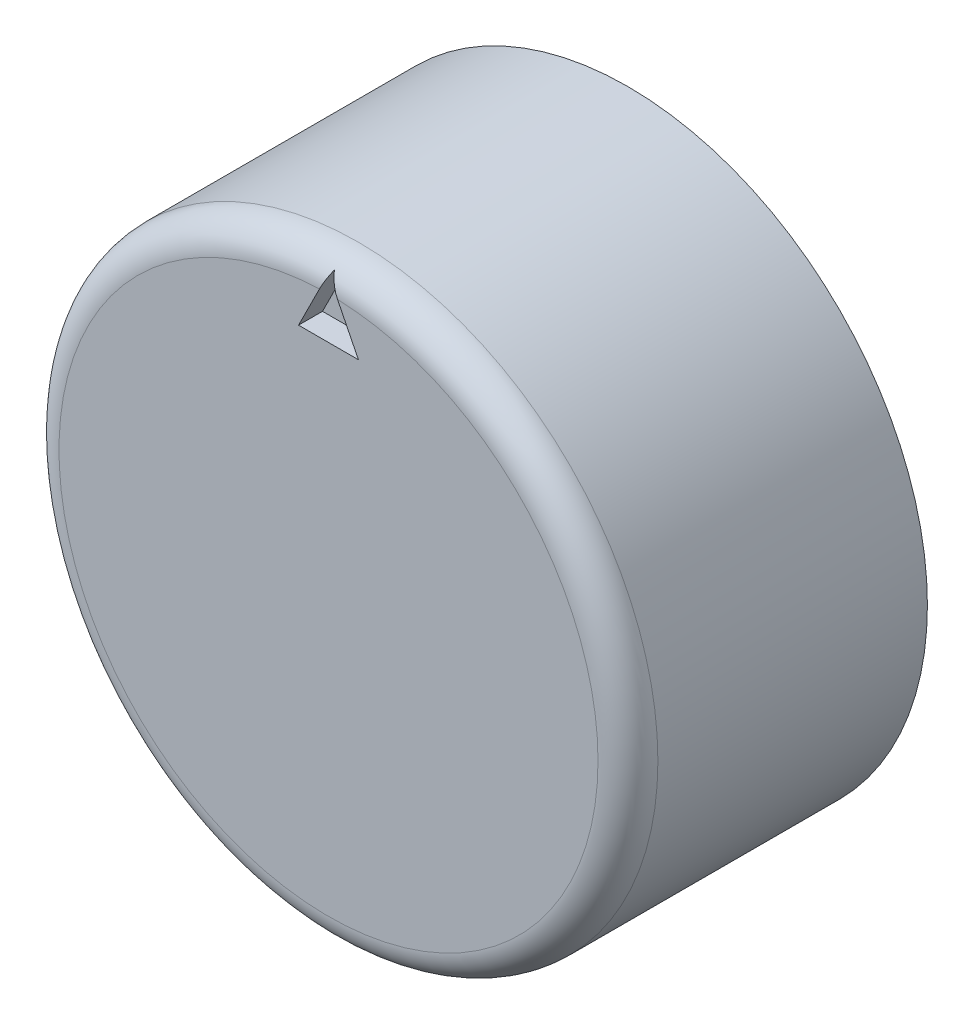
SolidWorks part; units mm, degrees
ref_plane "Front Plane" through (0, 0, 0) normal (0, 0, 1) x (1, 0, 0)
ref_plane "Top Plane" through (0, 0, 0) normal (0, 1, 0) x (1, 0, 0)
ref_plane "Right Plane" through (0, 0, 0) normal (1, 0, 0) x (0, 0, -1)
sketch "Sketch1" plane through (0, 0, 0) normal (0, 0, 1) x (1, 0, 0)
  circle A0 centre (0, 0) radius 12.7
  dimension "D1" = 25.4
extrude "Boss-Extrude1" add sketch "Sketch1" along normal blind 12.7
sketch "Sketch2" plane through (0, 0, 0) normal (0, 0, -1) x (-1, 0, 0)
  circle A0 centre (0, 0) radius 3.0988
  dimension "D1" = 6.1976
extrude "Cut-Extrude1" cut sketch "Sketch2" against normal blind 7.62 contours A0
sketch "Sketch3" plane through (0, 0, 7.62) normal (0, 0, -1) x (-1, 0, 0)
  line L0 (-3.0753, 0.381) -> (3.0753, 0.381)
  line L1 (-3.0753, -0.381) -> (3.0753, -0.381)
  circle A0 centre (0, 0) radius 3.0988 construction
  arc A1 (-3.0753, 0.381) -> (-3.0753, -0.381) centre (0, 0) ccw
  arc A4 (3.0753, 0.381) -> (3.0753, -0.381) centre (0, 0) cw
  point P8 (0, 0)
  dimension "D1" = 0.381
  dimension "D2" = 0.381
extrude "Boss-Extrude3" add sketch "Sketch3" along normal blind 1.016
sketch "Sketch4" plane through (0, 0, 0) normal (0, 0, -1) x (-1, 0, 0)
  circle A0 centre (0, 0) radius 5.08
  circle A1 centre (0, 0) radius 10.16
  dimension "D1" = 10.16
  dimension "D2" = 20.32
extrude "Cut-Extrude2" cut sketch "Sketch4" against normal blind 10.16
sketch "Sketch5" plane through (0, 0, 12.7) normal (0, 0, 1) x (1, 0, 0)
  line L0 (0, 12.192) -> (-1.27, 9.652)
  line L1 (-1.27, 9.652) -> (1.27, 9.652)
  line L3 (0, 12.192) -> (1.27, 9.652)
  circle A0 centre (0, 0) radius 12.7 construction
  dimension "D1" = 2.54
  dimension "D2" = 12.192
  dimension "D3" = 9.652
  dimension "D4" = 2.54
  dimension "D5" = 63.435
extrude "Cut-Extrude3" cut sketch "Sketch5" against normal blind 1.016 contours L0 L1 L3
fillet "Fillet1" radius 1.27 5 edges at (-10.16, 0, 10.16) (-5.08, 0, 10.16) (-3.0988, 0, 0) (-10.16, 0, 0) (12.7, 0, 12.7)
fillet "Fillet2" radius 0.381 2 edges at (0, 0.381, 6.604) (0, -0.381, 6.604)
equation "\"D1@Sketch3\"=0.03/2"
equation "\"D2@Sketch3\"=\"D1@Sketch3\""
